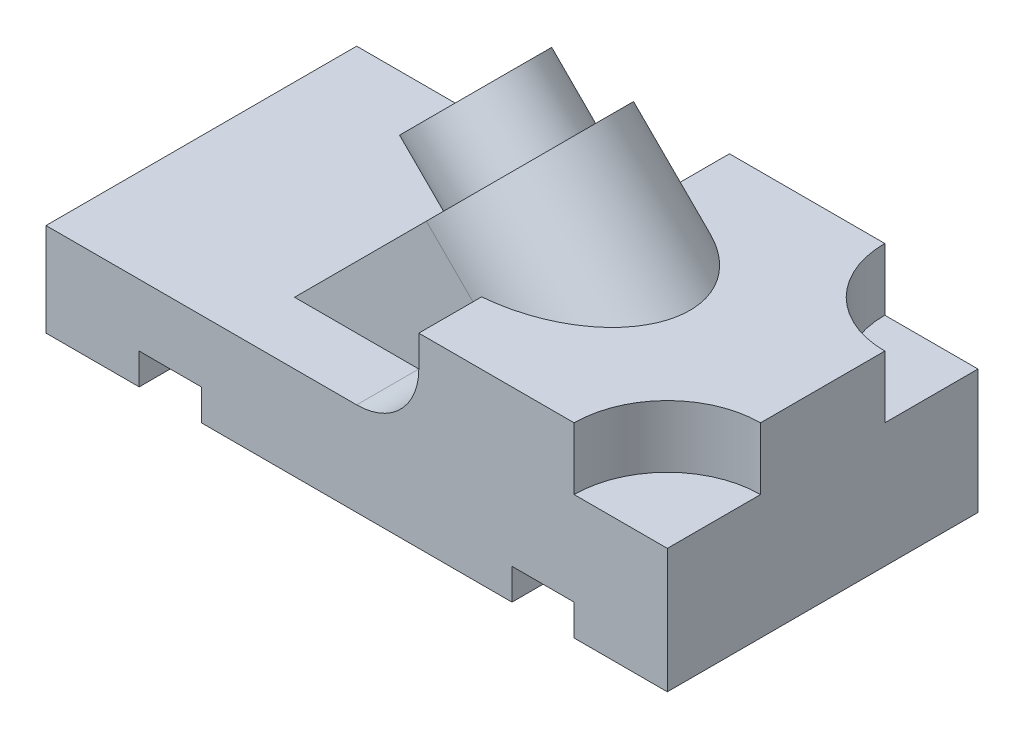
SolidWorks part; units mm, degrees
material "Ductile Iron"
ref_plane "Front Plane" through (0, 0, 0) normal (0, 0, 1) x (1, 0, 0)
ref_plane "Top Plane" through (0, 0, 0) normal (0, 1, 0) x (1, 0, 0)
ref_plane "Right Plane" through (0, 0, 0) normal (1, 0, 0) x (0, 0, -1)
sketch "Sketch1" plane through (0, 0, 0) normal (0, 0, 1) x (1, 0, 0)
  line L0 (0, 0) -> (100, 0)
  line L1 (100, 0) -> (100, 30)
  line L2 (100, 30) -> (60, 30)
  line L3 (60, 30) -> (60, 25)
  line L4 (50, 15) -> (0, 15)
  line L5 (0, 15) -> (0, 0)
  arc A0 (60, 25) -> (50, 15) centre (50, 25) cw
  dimension "D5" = 10
  dimension "D1" = 100
  dimension "D2" = 30
  dimension "D3" = 40
  dimension "D4" = 15
extrude "Boss-Extrude1" add sketch "Sketch1" against normal blind 50
ref_plane "Plane1" through (30, 0, 0) normal (-1, 0, 0) x (0, 0, 1)
ref_axis "Axis1" through (30, 15, -50) along (0, 0, 1)
ref_plane "Plane2" through (7.5, -7.5, 0) normal (-0.7071, 0.7071, 0) x (0, 0, 1)
sketch "Sketch2" plane through (7.5, -7.5, 0) normal (-0.7071, 0.7071, 0) x (0, 0, 1)
  line L0 (-40, 31.8268) -> (-10, 31.8268)
  line L1 (-10, 31.8268) -> (-10, 61.8268)
  line L2 (-40, 31.8268) -> (-40, 61.8268)
  line L3 (-40, 31.8268) -> (-50, 31.8268)
  line L4 (-10, 31.8268) -> (0, 31.8268)
  line L7 (0, 10.6066) -> (0, 45.9619)
  line L8 (0, 45.9619) -> (-50, 45.9619)
  line L9 (-50, 45.9619) -> (-50, 10.6066)
  line L10 (-50, 10.6066) -> (0, 10.6066)
  line L11 (0, 10.6066) -> (0, 45.9619)
  line L12 (0, 45.9619) -> (-50, 45.9619)
  line L13 (-50, 45.9619) -> (-50, 10.6066)
  line L14 (-50, 10.6066) -> (0, 10.6066)
  arc A0 (-40, 61.8268) -> (-10, 61.8268) centre (-25, 61.8268) cw
  dimension "D1" = 30
  dimension "D3" = 10
  dimension "D4" = 30
  dimension "D2" = 0
extrude "Boss-Extrude2" add sketch "Sketch2" against normal up to surface (0.007 mm away) contours L1 L12 L2 L0 | A0 L2 L12 L1 region at (35.0025, 20.0025, -25) region at (49.9176, 34.9176, -25) up to face at (25, 15, -25)
sketch "Sketch3" plane through (7.5, -7.5, 0) normal (-0.7071, 0.7071, 0) x (0, 0, 1)
  circle A0 centre (-25, 61.8268) radius 5
  circle A1 centre (-25, 61.8268) radius 10
  dimension "D1" = 20
  dimension "D2" = 10
extrude "Boss-Extrude3" add sketch "Sketch3" along normal blind 10
sketch "Sketch4" plane through (0, 30, 0) normal (0, 1, 0) x (1, 0, 0)
  circle A0 centre (100, 50) radius 15
  circle A1 centre (100, 0) radius 15
  dimension "D1" = 30
  dimension "D2" = 30
extrude "Cut-Extrude1" cut sketch "Sketch4" against normal blind 10
sketch "Sketch5" plane through (0, 0, 0) normal (0, 0, 1) x (1, 0, 0)
  line L0 (0, 0) -> (15, 0)
  line L1 (0, 0) -> (100, 0) construction
  line L2 (15, 0) -> (15, 5)
  line L3 (15, 5) -> (25, 5)
  line L4 (25, 5) -> (25, 0)
  line L5 (25, 0) -> (15, 0)
  line L6 (25, 0) -> (85, 0)
  line L7 (85, 0) -> (85, 5)
  line L8 (85, 5) -> (75, 5)
  line L9 (75, 5) -> (75, 0)
  line L10 (75, 0) -> (85, 0)
  line M14 (0, 0) -> (100, 0)
  dimension "D1" = 15
  dimension "D2" = 10
  dimension "D3" = 5
  dimension "D4" = 60
  dimension "D5" = 10
  dimension "D6" = 5
extrude "Cut-Extrude2" cut sketch "Sketch5" against normal through all contours L4 L3 L2 M14 | L8 L9 L6 L7 region at (80, 2.5, 0) region at (20, 2.5, 0)
